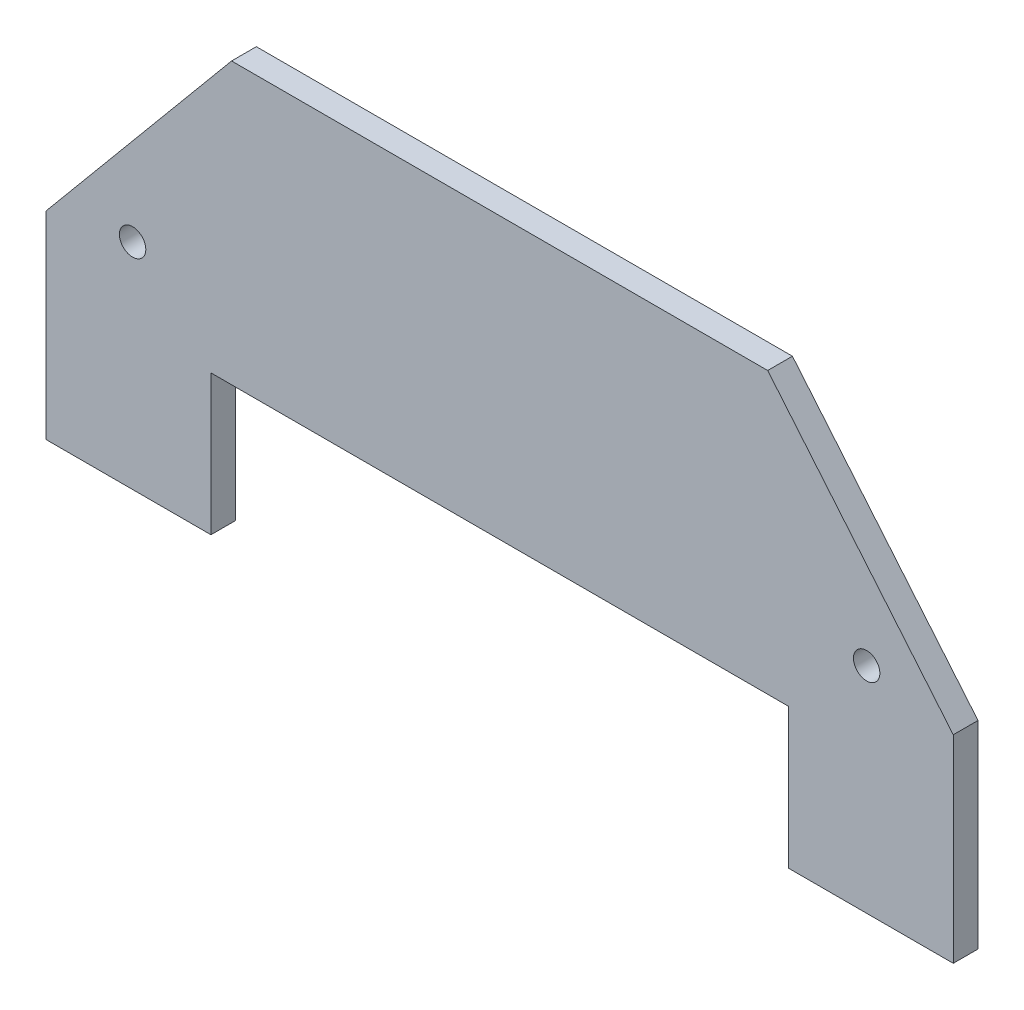
SolidWorks part; units mm, degrees
ref_plane "Alzado" through (0, 0, 0) normal (0, 0, 1) x (1, 0, 0)
ref_plane "Planta" through (0, 0, 0) normal (0, 1, 0) x (1, 0, 0)
ref_plane "Vista lateral" through (0, 0, 0) normal (1, 0, 0) x (0, 0, -1)
sketch "Croquis1" plane through (0, 0, 0) normal (0, 0, 1) x (1, 0, 0)
  line L0 (-55, 0) -> (55, 0)
  line L1 (55, 0) -> (55, 24)
  line L2 (55, 24) -> (32.5, 51)
  line L3 (32.5, 51) -> (-32.5, 51)
  line L4 (-32.5, 51) -> (-55, 24)
  line L5 (-55, 24) -> (-55, 0)
  point P2 (0, 51)
  dimension "D1" = 24
  dimension "D2" = 65
  dimension "D3" = 51
  dimension "D4" = 110
extrude "Saliente-Extruir1" add sketch "Croquis1" along normal blind 3
sketch "Croquis2" plane through (0, 0, 0) normal (0, 0, -1) x (-1, 0, 0)
  line L0 (-53.3333, 26) -> (53.3333, 26) construction
  line L1 (-55, 24) -> (-32.5, 51) construction
  line L2 (32.5, 51) -> (55, 24) construction
  line L3 (-44.5, 51) -> (-44.5, 0) construction
  line L4 (-32.5, 51) -> (32.5, 51) construction
  line L5 (55, 0) -> (-55, 0) construction
  line L6 (44.5, 51) -> (44.5, 0) construction
  line L7 (-55, 0) -> (-55, 24) construction
  line L8 (55, 24) -> (55, 0) construction
  dimension "D1" = 2
  dimension "D2" = 10.5
  dimension "D3" = 10.5
hole_wizard "Taladro de margen para M31" positions "Croquis3D1" profile "Croquis3" hole size "M3" standard "ISO"
sketch3d "Croquis3D1"
  line L0 (44.5, 51, 0) -> (44.5, 0, 0) construction
  line L1 (53.3333, 26, 0) -> (-53.3333, 26, 0) construction
  line L2 (-44.5, 51, 0) -> (-44.5, 0, 0) construction
  point P0 (44.5, 26, 0)
  point P6 (-44.5, 26, 0)
sketch "Croquis3" plane through (44.5, 26, 0) normal (1, 0, 0) x (0, 1, 0)
  line L0 (0, 0) -> (0, 5.9614)
  line L1 (0, 5.9614) -> (1.6, 5)
  line L2 (1.6, 5) -> (1.6, 0)
  line L5 (1.6, 0) -> (0, 0)
  line L10 (0, 5.9614) -> (-1.6, 5) construction
  line L11 (0, -6.35) -> (0, 107.95) construction
  dimension "Diámetro de taladro" = 3.2
  dimension "Profundidad de taladro" = 5
  dimension "Ángulo de perforador" = 118
sketch "Croquis4" plane through (0, 0, 3) normal (0, 0, 1) x (1, 0, 0)
  line L0 (-55, 0) -> (55, 0) construction
  line L1 (-35, 17) -> (35, 17)
  line L2 (-35, 17) -> (-35, 0)
  line L3 (-35, 0) -> (35, 0)
  line L4 (35, 17) -> (35, 0)
  line L6 (55, 0) -> (55, 24) construction
  line L7 (-55, 24) -> (-55, 0) construction
  dimension "D1" = 20
  dimension "D2" = 17
  dimension "D3" = 20
extrude "Cortar-Extruir1" cut sketch "Croquis4" against normal up to next
